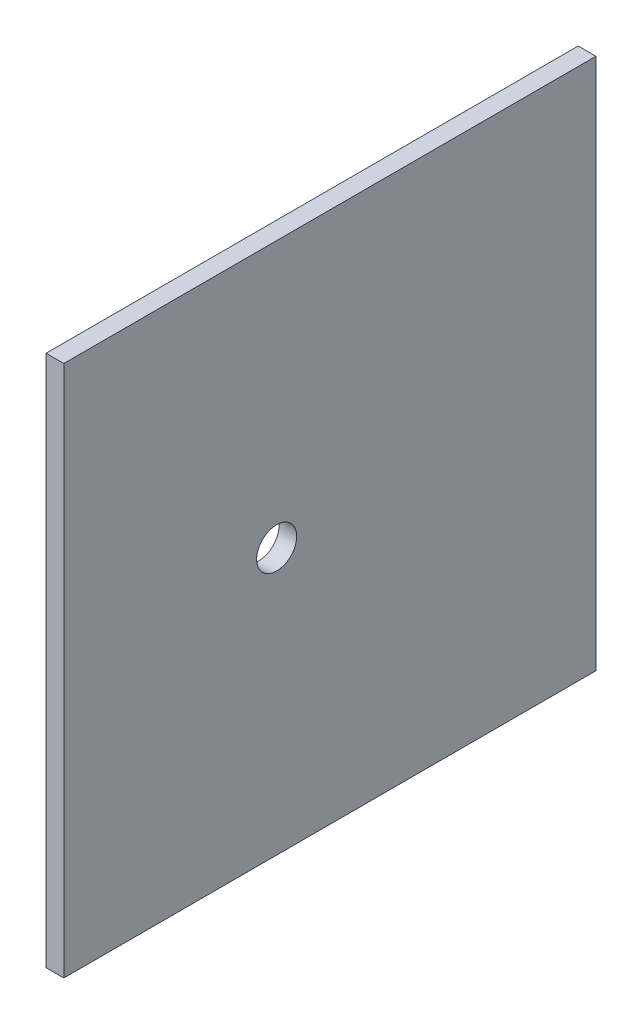
SolidWorks part; units mm, degrees
ref_plane "Front Plane" through (0, 0, 0) normal (0, 0, 1) x (1, 0, 0)
ref_plane "Top Plane" through (0, 0, 0) normal (0, 1, 0) x (1, 0, 0)
ref_plane "Right Plane" through (0, 0, 0) normal (1, 0, 0) x (0, 0, -1)
sketch "Sketch1" plane through (0, 0, 0) normal (1, 0, 0) x (0, 0, -1)
  line L1 (190.5, 190.5) -> (-190.5, 190.5)
  line L2 (190.5, 190.5) -> (190.5, -190.5)
  line L3 (190.5, -190.5) -> (-190.5, -190.5)
  line L4 (-190.5, 190.5) -> (-190.5, -190.5)
  line L5 (190.5, 190.5) -> (-190.5, -190.5) construction
  line L6 (190.5, -190.5) -> (-190.5, 190.5) construction
  circle A0 centre (-38.1, 0) radius 14.351
  point P0 (0, 0)
  dimension "D3" = 28.702
  dimension "D4" = 228.6
  dimension "D1" = 381
  dimension "D2" = 381
  dimension "D5" = 190.5
extrude "Boss-Extrude1" add sketch "Sketch1" along normal blind 12.7
